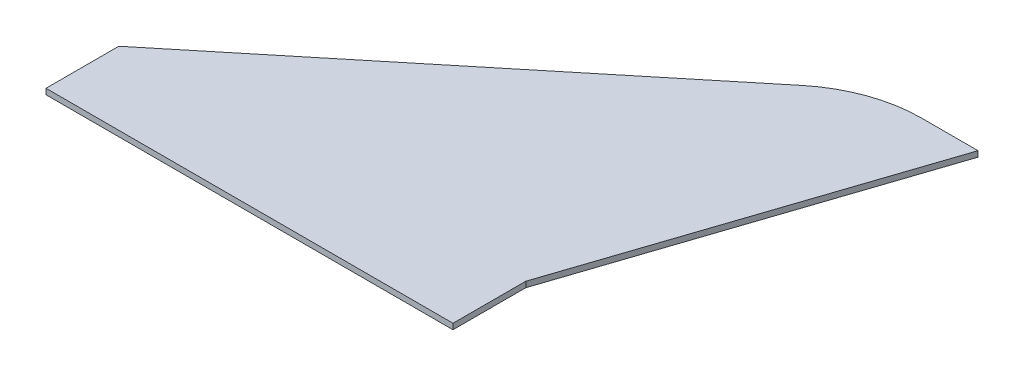
SolidWorks part; units mm, degrees
ref_plane "Front Plane" through (0, 0, 0) normal (0, 0, 1) x (1, 0, 0)
ref_plane "Top Plane" through (0, 0, 0) normal (0, 1, 0) x (1, 0, 0)
ref_plane "Right Plane" through (0, 0, 0) normal (1, 0, 0) x (0, 0, -1)
sketch "Sketch1" plane through (0, 0, 0) normal (0, 1, 0) x (1, 0, 0)
  line L0 (0, 40.894) -> (210.82, 213.614)
  line L1 (0, 0) -> (228.6, 0)
  line L2 (0, 0) -> (0, 40.894)
  line L4 (228.6, 0) -> (228.6, 40.894)
  line L6 (292.1, 231.394) -> (228.6, 40.894)
  line L7 (292.1, 231.394) -> (260.5775, 231.394)
  line L8 (0, 40.894) -> (228.6, 40.894) construction
  arc A0 (260.5775, 231.394) -> (210.82, 213.614) centre (260.5775, 152.8806) ccw
  point P8 (228.6, 40.894)
  dimension "D1" = 228.6
  dimension "D2" = 172.72
  dimension "D3" = 190.5
  dimension "D4" = 210.82
  dimension "D5" = 292.1
  dimension "D6" = 40.894
  dimension "D7" = 260.5775
  dimension "D8" = 228.6
extrude "Boss-Extrude1" add sketch "Sketch1" along normal blind 3.175 contours L1 L4 L2 | L6 L0 region at (158.5332, 0, -92.5397)
